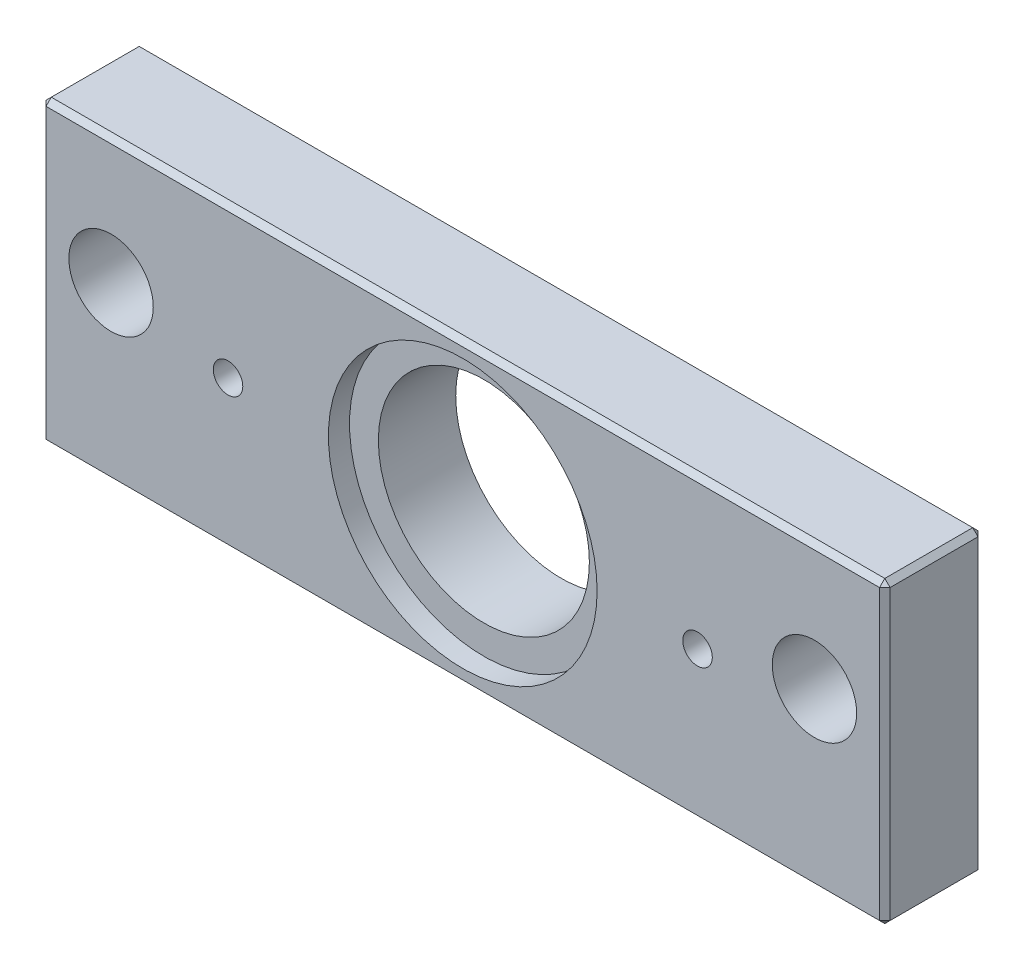
SolidWorks part; units mm, degrees
ref_plane "Front Plane" through (0, 0, 0) normal (0, 0, 1) x (1, 0, 0)
ref_plane "Top Plane" through (0, 0, 0) normal (0, 1, 0) x (1, 0, 0)
ref_plane "Right Plane" through (0, 0, 0) normal (1, 0, 0) x (0, 0, -1)
sketch "Sketch1" plane through (0, 0, 0) normal (0, 0, 1) x (1, 0, 0)
  line L1 (-60, -21.25) -> (60, -21.25)
  line L2 (-60, -21.25) -> (-60, 21.25)
  line L3 (-60, 21.25) -> (60, 21.25)
  line L4 (60, -21.25) -> (60, 21.25)
  line L5 (-60, -21.25) -> (60, 21.25) construction
  line L6 (-60, 21.25) -> (60, -21.25) construction
  point P0 (0, 0)
  dimension "D1" = 120
  dimension "D2" = 42.5
extrude "Boss-Extrude1" add sketch "Sketch1" along normal mid plane 14
sketch "Sketch2" plane through (0, 0, 7) normal (0, 0, 1) x (1, 0, 0)
  circle A0 centre (0, 0) radius 19.1
  dimension "D1" = 38.2
extrude "Cut-Extrude1" cut sketch "Sketch2" against normal blind 3
sketch "Sketch3" plane through (0, 0, 4) normal (0, 0, 1) x (1, 0, 0)
  circle A0 centre (0, 0) radius 15
extrude "Cut-Extrude2" cut sketch "Sketch3" against normal through all
sketch "Sketch4" plane through (0, 0, 7) normal (0, 0, 1) x (1, 0, 0)
  circle A0 centre (-33.375, 0) radius 2.1
  circle A1 centre (33.375, 0) radius 2.1
  dimension "D1" = 4.2
  dimension "D2" = 4.2
  dimension "D3" = 33.375
  dimension "D4" = 33.375
extrude "Cut-Extrude3" cut sketch "Sketch4" against normal through all
sketch "Sketch5" plane through (0, 0, 7) normal (0, 0, 1) x (1, 0, 0)
  line L0 (-40.6477, 3.4) -> (36.4799, 3.4) construction
  circle A0 centre (-50, 3.4) radius 6
  circle A1 centre (50, 3.4) radius 6
  dimension "D1" = 12
  dimension "D2" = 12
  dimension "D4" = 50
  dimension "D3" = 50
  dimension "D5" = 3.4
extrude "Cut-Extrude4" cut sketch "Sketch5" against normal through all
sketch "Sketch6" plane through (0, -21.25, 0) normal (0, -1, 0) x (1, 0, 0)
  line L0 (-60, 0) -> (60, 0) construction
  line L1 (-60, 7) -> (-60, -7) construction
  line L2 (60, 7) -> (60, -7) construction
  circle A0 centre (-50, 0) radius 2.1
  circle A1 centre (-25, 0) radius 2.1
  circle A2 centre (25, 0) radius 2.1
  circle A3 centre (50, 0) radius 2.1
  circle A4 centre (-37.5, 0) radius 1.25
  circle A5 centre (37.5, 0) radius 1.25
  dimension "D1" = 4.2
  dimension "D2" = 4.2
  dimension "D3" = 4.2
  dimension "D4" = 4.2
  dimension "D5" = 10
  dimension "D9" = 2.5
  dimension "D10" = 2.5
  dimension "D11" = 22.5
  dimension "D12" = 22.5
  dimension "D6" = 35
  dimension "D7" = 10
  dimension "D8" = 35
extrude "Cut-Extrude5" cut sketch "Sketch6" against normal blind 10
chamfer "Chamfer1" distance 0.75 angle 45 12 edges at (60, -21.25, 0) (60, 0, -7) (60, 21.25, 0) (0, -21.25, -7) (-60, -21.25, 0) (-60, 0, -7) (0, 21.25, -7) (-60, 21.25, 0) (60, 0, 7) (0, -21.25, 7) (-60, 0, 7) (0, 21.25, 7)
equation "\"D4@Sketch4\"=\"D3@Sketch4\""
